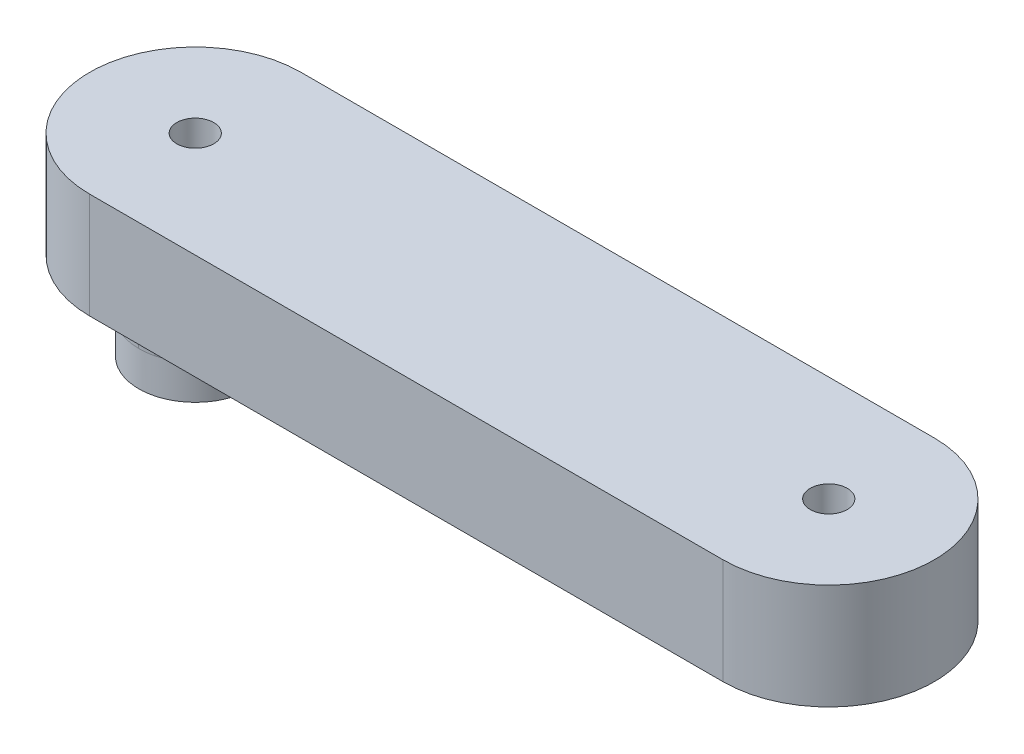
SolidWorks part; units mm, degrees
material "PLA"
ref_plane "Front Plane" through (0, 0, 0) normal (0, 0, 1) x (1, 0, 0)
ref_plane "Top Plane" through (0, 0, 0) normal (0, 1, 0) x (1, 0, 0)
ref_plane "Right Plane" through (0, 0, 0) normal (1, 0, 0) x (0, 0, -1)
sketch "Sketch1" plane through (0, 0, 0) normal (0, 1, 0) x (1, 0, 0)
  line L0 (-30, 0) -> (30, 0) construction
  line L1 (-30, 10) -> (30, 10)
  line L2 (-30, -10) -> (30, -10)
  arc A0 (-30, 10) -> (-30, -10) centre (-30, 0) ccw
  arc A1 (30, -10) -> (30, 10) centre (30, 0) ccw
  point P3 (0, 0)
  dimension "D1" = 10
  dimension "D2" = 60
extrude "Boss-Extrude1" add sketch "Sketch1" along normal blind 10
sketch "Sketch2" plane through (0, 10, 0) normal (0, 1, 0) x (1, 0, 0)
  circle A5 centre (30, 0) radius 1.75
  dimension "D1" = 3.5
extrude "Cut-Extrude1" cut sketch "Sketch2" against normal up to next
sketch "Sketch5" plane through (0, 0, 0) normal (0, -1, 0) x (1, 0, 0)
  circle A0 centre (-30, 0) radius 5.35
  dimension "D1" = 10.7
extrude "Boss-Extrude3" add sketch "Sketch5" along normal blind 8.3
fillet "Fillet1" radius 5 1 edges at (-30, 0, 5.35)
sketch "Sketch6" plane through (0, -8.3, 0) normal (0, -1, 0) x (-1, 0, 0)
  circle A0 centre (30, 0) radius 1.75
  dimension "D1" = 3.5
extrude "Cut-Extrude2" cut sketch "Sketch6" against normal up to next
equation "\"Length\"= 60mm"
equation "\"Radius\"= 10mm"
equation "\"D1@Sketch1\"= \"Radius\""
equation "\"D2@Sketch1\" = \"Length\""
equation "\"Thick\"= 10mm"
equation "\"D1@Boss-Extrude1\"= \"Thick\""
equation "\"D1@Boss-Extrude3\"=9.00-0.7"
